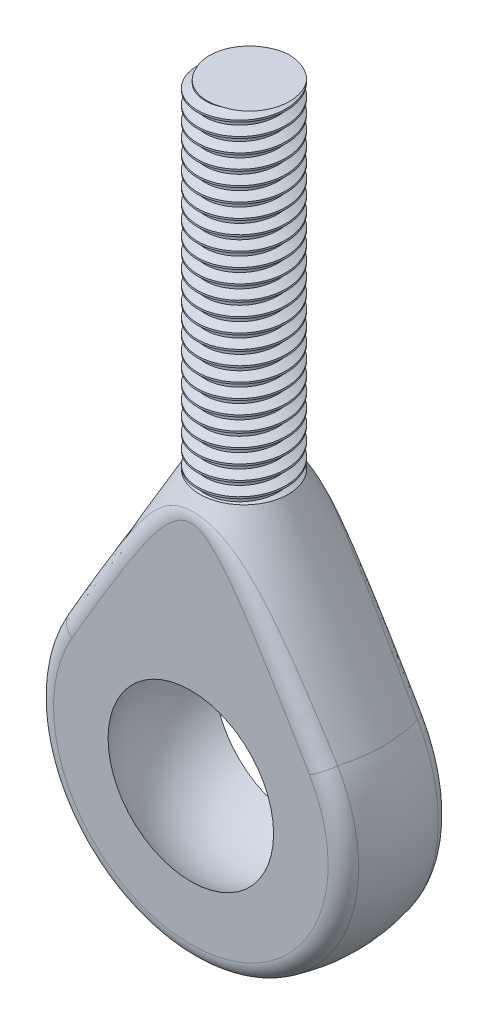
SolidWorks part; units mm, degrees
material "1060 Alloy"
ref_plane "Front Plane" through (0, 0, 0) normal (0, 0, 1) x (1, 0, 0)
ref_plane "Top Plane" through (0, 0, 0) normal (0, 1, 0) x (1, 0, 0)
ref_plane "Right Plane" through (0, 0, 0) normal (1, 0, 0) x (0, 0, -1)
sketch "Sketch1" plane through (0, 0, 0) normal (0, 0, 1) x (1, 0, 0)
  line L0 (0, -319.6475) -> (0, 15662.728) construction
  line L1 (2.5, 14) -> (2.5, 33)
  line L2 (2.5, 33) -> (-2.5, 33)
  line L3 (-2.5, 33) -> (-2.5, 14)
  line L4 (-7.8612, 4.3819) -> (-2.5, 14)
  line L6 (2.5, 14) -> (7.8612, 4.3819)
  circle A0 centre (0, 0) radius 5.55
  arc A1 (-7.8612, 4.3819) -> (7.8612, 4.3819) centre (0, 0) ccw
  point P3 (0, -9)
  point P9 (0, 33)
  dimension "D2" = 11.1
  dimension "D3" = 9
  dimension "D1" = 42
  dimension "D4" = 5
  dimension "D5" = 19
revolve "Revolve2" add sketch "Sketch1" angle 360 about L0 region at (3.2746, 9.1166, 0)
ref_plane "Plane1" through (0, 0, 3) normal (0, 0, 1) x (1, 0, 0)
sketch "Sketch3" plane through (0, 0, 3) normal (0, 0, 1) x (1, 0, 0)
  line L1 (-10.0912, -33) -> (10.0912, -33)
  line L2 (-10.0912, -33) -> (-10.0912, 33)
  line L3 (-10.0912, 33) -> (10.0912, 33)
  line L4 (10.0912, -33) -> (10.0912, 33)
  line L5 (-10.0912, -33) -> (10.0912, 33) construction
  line L6 (-10.0912, 33) -> (10.0912, -33) construction
  point P0 (0, 0)
extrude "Cut-Extrude6" cut sketch "Sketch3" along normal through all
mirror "Mirror1" about plane through (0, 0, 0) normal (0, 0, 1) of "Cut-Extrude6"
thread "Thread1" pitch 0.8 method cut profile "Thread Profile1" start angle 0, offset 1, length 0, pitch 0.8, diameter 5
ref_plane "Plane2" through (-2.5, 34, 0) normal (0, 0, 1) x (-1, 0, 0)
sketch "Thread Profile1" plane through (-2.5, 34, 0) normal (0, 0, 1) x (-1, 0, 0)
  line L0 (0, 0) -> (0, 0.8) construction
  line L11 (0, 0) -> (0, 0.7)
  line L12 (0, 0.7) -> (-0.433, 0.45)
  line L13 (-0.433, 0.45) -> (-0.433, 0.25)
  line L15 (-0.433, 0.25) -> (0, 0)
  line L17 (-0.433, 0.35) -> (0, 0.35) construction
  point P2 (0, 0)
  dimension "Pitch" = 0.8
  dimension "Profile_Angle" = 60
  dimension "Profile_Land" = 0.2
  dimension "Profile_Height" = 0.433
fillet "Fillet1" radius 1 4 edges at (0, -8.4853, -3) (0, -8.4853, 3) (-0.5063, 13.0269, -3) (-0.5063, 13.0269, 3)
ref_axis "Axis1" through (0, 0, -5.5523) along (0, 0, 1)
